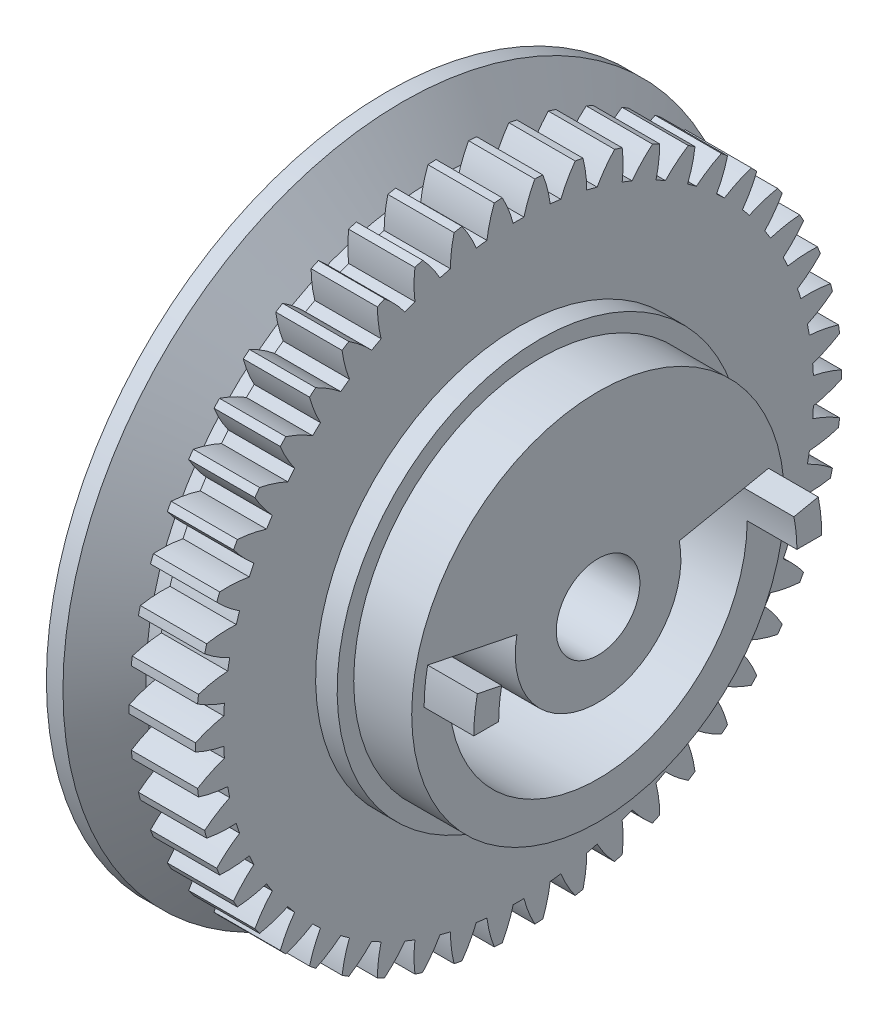
SolidWorks part; units mm, degrees
ref_plane "Plane1" through (0, 0, 0) normal (0, 0, 1) x (1, 0, 0)
ref_plane "Plane2" through (0, 0, 0) normal (0, 1, 0) x (1, 0, 0)
ref_plane "Plane3" through (0, 0, 0) normal (1, 0, 0) x (0, 0, -1)
other "Configuration Table"
sketch "HoldingSke" plane through (0, 0, 0) normal (0, 1, 0) x (1, 0, 0)
  line L0 (0, 0) -> (0.4285, -0.5107)
  line L1 (-15, 0) -> (100, 0) construction
  line L2 (0, 0) -> (-2.1039, 2.3779)
  line L3 (0, 0) -> (-11.863, 4.5341)
  line L4 (0, 0) -> (5.5511, 6.6156)
  line L5 (0, 0) -> (-46.8476, -17.4728)
  line L6 (0, 0) -> (-6.6317, -4.4744)
  line L7 (-2.1039, 2.3779) -> (8.6586, 51.2059)
  line L8 (-76.2, 54.61) -> (-74.4, 54.61)
  line L9 (-71.009, 38.7566) -> (-53.1078, 45.2721)
  line L10 (-76.2, 71.12) -> (104.1128, 71.12)
  line L11 (0, 0) -> (-8, 0)
  line L12 (-76.2, 101.6) -> (-76.147, 101.6)
  line L13 (24.9733, 27.94) -> (52.9518, 28.4284)
  line L14 (24.9733, 27.94) -> (24.9743, 27.94)
  line L15 (24.9733, 27.94) -> (100.4006, 29.5858)
  line L16 (-63.627, -1.5) -> (-12.827, -1.5)
  circle A0 centre (0, 0) radius 5
  circle A1 centre (0, 0) radius 35.624
  circle A2 centre (0, 0) radius 37.5
  circle A3 centre (0, 0) radius 5
  dimension "MHD" = 71.248
  dimension "Hub_dia" = 75
  dimension "Bore" = 10
  dimension "MBD" = 10
  dimension "Num_teeth" = 50
  dimension "Pitch" = 0.6667
  dimension "Overall_len" = 50
  dimension "Show_teeth" = 50
  dimension "Thickness" = 8
  dimension "OAL" = 50.0001
  dimension "T_dim" = 1.8
  dimension "Ap" = 20
  dimension "H" = 19.05
  dimension "Pitch_radius" = 180.3128
  dimension "Width" = 8
  dimension "Backlash" = 0.053
  dimension "Addendum_fac" = 1
  dimension "Dedendum_fac" = 1.25
  dimension "Clearance_fac" = 0.25
  dimension "Dedendum_add" = 0.001
  dimension "Module" = 1.5
sketch "BasProSke" plane through (0, 0, 0) normal (0, 1, 0) x (1, 0, 0)
  line L0 (-10, 0) -> (60, 0) construction
  line L1 (0, 0) -> (0, 39)
  line L2 (0, 0) -> (8, 0)
  line L3 (8, 0) -> (8, 39)
  line L4 (8, 39) -> (0, 39)
  dimension "Thickness" = 8
  dimension "Diameter" = 78
revolve "Base-Revolve" add sketch "BasProSke" angle 360 about L0
sketch "TooCutSke" plane through (0, 0, 0) normal (1, 0, 0) x (0, 0, -1)
  line L1 (0, 0) -> (0, 107) construction
  line L2 (0, 0) -> (-1.2706, 37.4785) construction
  line L3 (0, 0) -> (-4.7073, 74.8207) construction
  line L4 (-1.2706, 37.4785) -> (-2.3537, 37.4103) construction
  arc A0 (0.65, 35.6181) -> (-0.65, 35.6181) centre (0, 0) ccw
  arc A1 (1.9801, 38.9751) -> (-1.9801, 38.9751) centre (0, 0) ccw
  circle A2 centre (0, 0) radius 37.5 construction
  circle A3 centre (0, 0) radius 35.2385 construction
  arc A4 (-0.65, 35.6181) -> (-1.9801, 38.9751) centre (-15.1589, 31.8113) ccw
  arc A5 (1.9801, 38.9751) -> (0.65, 35.6181) centre (15.1589, 31.8113) ccw
  dimension "Root_dia" = 71.248
  dimension "Overcut_dia" = 78.0508
  dimension "Pitch_dia" = 75
  dimension "Base_dia" = 70.4769
  dimension "Flank_rad" = 15
  dimension "Half_ang" = 3.6
  dimension "Half_CT" = 1.0852
extrude "ToothCut" cut sketch "TooCutSke" along normal through all
fillet "Breaks" [suppressed] radius 0.03 tangent propagation no
fillet "RootFillets" [suppressed] radius 0.376
pattern_circular "TeethCuts" count 50 every 7.2 about axis through (-10, 0, 0) along (1, 0, 0) of "ToothCut", "RootFillets", "Breaks"
sketch "HubNeaOneSke" plane through (0, 0, 0) normal (-1, 0, 0) x (0, 0, 1)
  circle A0 centre (0, 0) radius 35.624
  dimension "Diameter" = 71.248
extrude "HubNearOne" [suppressed] add sketch "HubNeaOneSke" along normal blind 42.0001
sketch "HubNeaBotSke" plane through (0, 0, 0) normal (-1, 0, 0) x (0, 0, 1)
  circle A0 centre (0, 0) radius 35.624
  dimension "Diameter" = 71.248
extrude "HubNearBoth" [suppressed] add sketch "HubNeaBotSke" along normal blind 21
ref_plane "FarPln" through (8, 0, 0) normal (1, 0, 0) x (0, 0, -1)
sketch "HubFarSke" plane through (8, 0, 0) normal (1, 0, 0) x (0, 0, -1)
  circle A0 centre (0, 0) radius 35.624
  dimension "Diameter" = 71.248
extrude "HubFar" [suppressed] add sketch "HubFarSke" along normal blind 21
sketch "BorSke" plane through (0, 0, 0) normal (1, 0, 0) x (0, 0, -1)
  circle A0 centre (0, 0) radius 5
  dimension "Diameter" = 10
extrude "Bore" cut sketch "BorSke" along normal mid plane 100.0001
sketch "KeySke" plane through (0, 0, 0) normal (1, 0, 0) x (0, 0, -1)
  line L0 (-2, 0) -> (-2, 6.8)
  line L1 (-2, 6.8) -> (2, 6.8)
  line L2 (2, 6.8) -> (2, 0)
  line L3 (0, 0) -> (0, 34) construction
  line L4 (-2, 0) -> (2, 0)
  dimension "Offset" = 6.8
  dimension "Width" = 4
extrude "Keyway" [suppressed] cut sketch "KeySke" along normal mid plane 100.0001
pattern_circular "Keyway2" [suppressed] count 2 every 90 about axis through (-10, 0, 0) along (1, 0, 0) reverse direction yes
sketch "草图1" plane through (0, 0, 0) normal (0, 0, 1) x (1, 0, 0)
  line L0 (8, 24.5) -> (10.6, 24.5)
  line L1 (8, -5) -> (8, 5) construction
  line L2 (10.6, 24.5) -> (10.6, 22.5)
  line L3 (10.6, 22.5) -> (17.6, 22.5)
  line L4 (17.6, 22.5) -> (17.6, 5)
  line L5 (17.6, 5) -> (8, 5)
  line L6 (8, 5) -> (8, 24.5)
  line L7 (-8, 5) -> (0, 5)
  line L8 (0, 0) -> (-5.2993, 0) construction
  line L9 (0, 0.4829) -> (0, -0.4829) construction
  line L10 (0, 5) -> (0, 35)
  line L11 (0, 35) -> (-2, 35)
  line L12 (-2, 35) -> (-6, 41)
  line L13 (-6, 41) -> (-8, 41)
  line L14 (-8, 41) -> (-8, 5)
  line L15 (0, 0) -> (0, 107) construction
  dimension "D1" = 45
  dimension "D2" = 2
  dimension "D3" = 2.6
  dimension "D4" = 7
  dimension "D5" = 10
  dimension "D6" = 82
  dimension "D7" = 70
  dimension "D8" = 2
  dimension "D9" = 2
  dimension "D10" = 8
revolve "旋转1" add sketch "草图1" angle 360 about L8
ref_axis "基准轴1" through (17.6, 0, 0) along (-1, 0, 0)
sketch "草图2" plane through (-8, 0, 0) normal (-1, 0, 0) x (0, 0, 1)
  circle A0 centre (0, 0) radius 7.5
  dimension "D1" = 15
extrude "切除-拉伸1" cut sketch "草图2" against normal blind 5.5
sketch "草图10" plane through (-8, 0, 0) normal (-1, 0, 0) x (0, 0, 1)
  circle A0 centre (0, 0) radius 5.05
  point P2 (0, 0)
  point P3 (0, 0)
  dimension "D1" = 10.1
extrude "切除-拉伸5" cut sketch "草图10" against normal through all
sketch "草图3" plane through (-8, 0, 0) normal (-1, 0, 0) x (0, 0, 1)
  line L0 (0, 0) -> (0, -18.4341) construction
  arc A0 (-7.5, -6.6144) -> (7.5, -6.6144) centre (0, 0) ccw
  arc A1 (-13.5, -11.9059) -> (13.5, -11.9059) centre (0, 0) ccw
  arc A2 (-13.5, -11.9059) -> (-7.5, -6.6144) centre (-10.5, -9.2601) cw
  arc A3 (7.5, -6.6144) -> (13.5, -11.9059) centre (10.5, -9.2601) cw
  dimension "D1" = 10
  dimension "D2" = 18
  dimension "D3" = 15
extrude "切除-拉伸2" cut sketch "草图3" against normal through all
sketch "草图4" plane through (17.6, 0, 0) normal (1, 0, 0) x (0, 0, -1)
  line L0 (14, 0) -> (-14, 0) construction
  circle A0 centre (-14, 0) radius 1.1
  circle A1 centre (14, 0) radius 1.1
  point P8 (0, 0)
  dimension "D3" = 2.2
  dimension "D1" = 28
extrude "切除-拉伸3" cut sketch "草图4" against normal up to surface (25.6 mm away) up to face at (-8, -10.1301, 0)
sketch "草图5" plane through (17.6, 0, 0) normal (1, 0, 0) x (0, 0, -1)
  line L0 (-17.6363, 3.6) -> (-9.798, 2)
  line L1 (17.6363, 3.6) -> (9.798, 2)
  line L2 (-7.6844, 0) -> (0, 0) construction
  arc A1 (9.798, 2) -> (-9.798, 2) centre (0, 0) cw
  arc A3 (17.6363, 3.6) -> (-17.6363, 3.6) centre (0, 0) cw
  arc A6 (-13.5, -11.9059) -> (13.5, -11.9059) centre (0, 0) ccw construction
  arc A7 (-7.5, -6.6144) -> (7.5, -6.6144) centre (0, 0) ccw construction
  dimension "D1" = 2
extrude "切除-拉伸4" cut sketch "草图5" against normal offset from surface (13.6 mm away) 12 up to face at (-8, -1.1, -14)
sketch "草图7" plane through (17.6, 0, 0) normal (1, 0, 0) x (0, 0, -1)
  line L0 (17.6363, 3.6) -> (20.5757, 4.2)
  line L1 (18, 0) -> (21, 0)
  line L2 (-17.6363, 3.6) -> (-20.5757, 4.2)
  line L3 (-18, 0) -> (-21, 0)
  circle A0 centre (0, 0) radius 18
  circle A1 centre (0, 0) radius 21
  arc A2 (-17.6363, 3.6) -> (17.6363, 3.6) centre (0, 0) ccw construction
  arc M10 (17.6363, 3.6) -> (-17.6363, 3.6) centre (0, 0) cw
  dimension "D1" = 3
extrude "凸台-拉伸1" add sketch "草图7" along normal blind 6 contours L2 A1 L3 M10 | L1 A1 L0 M10 region at (17.6, 1.9605, -19.4067) region at (17.6, 1.9605, 19.4067)
equation "' \"Module@HoldingSke\" = 6.35"
equation "' \"Num_teeth@HoldingSke\" = 12"
equation "' \"Ap@HoldingSke\" =  20"
equation "' \"Ap@HoldingSke\" = 20"
equation "' \"Width@HoldingSke\" = 0.5 * 25.4"
equation "' \"Hub_dia@HoldingSke\"= 1 * 25.4"
equation "' \"Hub_dia@HoldingSke\" = 1 * 25.4"
equation "' \"Overall_len@HoldingSke\" = 1.0 * 25.4"
equation "' \"Bore@HoldingSke\" = 0.75 * 25.4"
equation "' \"T_dim@HoldingSke\" = 0.1 * 25.4"
equation "' \"Width@KeySke\" = 0.25 * 25.4"
equation "' \"Show_teeth@HoldingSke\" = 13"
equation "' \"Backlash@HoldingSke\" = 0.009 * 25.4"
equation "' \"Addendum_fac@HoldingSke\" = 1.0"
equation "' \"Dedendum_fac@HoldingSke\" = 1.25"
equation "' \"Dedendum_add@HoldingSke\" = 0.00005 * 25.4"
equation "' \"Clearance_fac@HoldingSke\" = 0.25"
equation "\"Pitch@HoldingSke\" = 1 / \"Module@HoldingSke\""
equation "\"Overcut_dia@TooCutSke\" = (\"Num_teeth@HoldingSke\" + 2 * \"Addendum_fac@HoldingSke\") / \"Pitch@HoldingSke\" + 0.002 * 25.4"
equation "\"Pitch_dia@TooCutSke\" = \"Num_teeth@HoldingSke\" / \"Pitch@HoldingSke\""
equation "\"Base_dia@TooCutSke\" = \"Num_teeth@HoldingSke\" / \"Pitch@HoldingSke\" * cos((\"Ap@HoldingSke\"  * 3.14159265 / 180))"
equation "\"Root_dia@TooCutSke\" = (\"Num_teeth@HoldingSke\" + 2) / \"Pitch@HoldingSke\" - 2 * (\"Addendum_fac@HoldingSke\" + \"Dedendum_fac@HoldingSke\") / \"Pitch@HoldingSke\" - \"Dedendum_add@HoldingSke\" * 2"
equation "\"Half_ang@TooCutSke\" = 180 / \"Num_teeth@HoldingSke\""
equation "\"Half_CT@TooCutSke\" = \"Num_teeth@HoldingSke\" / \"Pitch@HoldingSke\" * sin((3.14159265 / 2 / \"Num_teeth@HoldingSke\")) / 2 - 7 * \"Backlash@HoldingSke\" / 4"
equation "\"Flank_rad@TooCutSke\" = \"Num_teeth@HoldingSke\" / \"Pitch@HoldingSke\" / 5"
equation "\"Radius@RootFillets\" = \"Clearance_fac@HoldingSke\" / \"Pitch@HoldingSke\" + \"Dedendum_add@HoldingSke\""
equation "\"Break_rad@Breaks\" = 0.02 / \"Pitch@HoldingSke\""
equation "\"Thickness@HoldingSke\" = \"Width@HoldingSke\""
equation "\"OAL@HoldingSke\" = \"Thickness@HoldingSke\""
equation "\"MHD@HoldingSke\" = (\"Num_teeth@HoldingSke\" + 2) / \"Pitch@HoldingSke\" - 2 * (\"Addendum_fac@HoldingSke\" + \"Dedendum_fac@HoldingSke\")  / \"Pitch@HoldingSke\" - \"Dedendum_add@HoldingSke\" * 2"
equation "\"MBD@HoldingSke\" = (\"Num_teeth@HoldingSke\" + 2) / \"Pitch@HoldingSke\" - 2 * (\"Addendum_fac@HoldingSke\" + \"Dedendum_fac@HoldingSke\")  / \"Pitch@HoldingSke\" - \"Dedendum_add@HoldingSke\" * 2 - 0.002 * 25.4"
equation "\"MHD@HoldingSke\" = ((sgn( \"MHD@HoldingSke\" - \"Hub_dia@HoldingSke\" )-1)*( \"MHD@HoldingSke\" - \"Hub_dia@HoldingSke\" ))/-2+ \"Hub_dia@HoldingSke\""
equation "\"MBD@HoldingSke\" = ((sgn( \"MBD@HoldingSke\" - \"Bore@HoldingSke\" )-1)*( \"MBD@HoldingSke\" - \"Bore@HoldingSke\" ))/-2+ \"Bore@HoldingSke\""
equation "\"OAL@HoldingSke\" = ((sgn( \"OAL@HoldingSke\" - \"Overall_len@HoldingSke\" )+1)*( \"OAL@HoldingSke\" - \"Overall_len@HoldingSke\" ))/2 + \"Overall_len@HoldingSke\" + 0.000002 * 25.4"
equation "\"Num_teeth@TeethCuts\" = int( \"Show_teeth@HoldingSke\" ) + 1"
equation "\"Num_teeth@TeethCuts\" = ((sgn( \"Num_teeth@TeethCuts\" - \"Num_teeth@HoldingSke\" )-1)*( \"Num_teeth@TeethCuts\" - \"Num_teeth@HoldingSke\" ))/-2+ \"Num_teeth@HoldingSke\""
equation "\"Num_teeth@TeethCuts\" = ((sgn( \"Num_teeth@TeethCuts\" - 2.0)+1)*( \"Num_teeth@TeethCuts\" - 2.0))/2 +2.0"
equation "\"Angle@TeethCuts\" = 360.0 / \"Num_teeth@HoldingSke\""
equation "\"Diameter@BasProSke\" = (\"Num_teeth@HoldingSke\" + 2 * \"Addendum_fac@HoldingSke\") / \"Pitch@HoldingSke\""
equation "\"Thickness@BasProSke\"  = \"Thickness@HoldingSke\""
equation "' \"Fillet_rad@BasProSke\" =  \"Thickness@HoldingSke\" * 0.05"
equation "' \"Fillet_rad@BasProSke\" = \"Thickness@HoldingSke\" * 0.05"
equation "\"MHD@HoldingSke\" = ((sgn( \"MHD@HoldingSke\" - \"Root_dia@TooCutSke\" )-1)*( \"MHD@HoldingSke\" - \"Root_dia@TooCutSke\" ))/-2+ \"Root_dia@TooCutSke\""
equation "\"Diameter@HubNeaOneSke\" = \"MHD@HoldingSke\""
equation "\"Length@HubNearOne\" = \"OAL@HoldingSke\" - \"Thickness@BasProSke\""
equation "\"Diameter@HubNeaBotSke\" = \"MHD@HoldingSke\""
equation "\"Length@HubNearBoth\" = ( \"OAL@HoldingSke\" - \"Thickness@BasProSke\" ) / 2.0"
equation "\"Thickness@FarPln\" = \"Thickness@BasProSke\""
equation "\"Diameter@HubFarSke\" = \"MHD@HoldingSke\""
equation "\"Length@HubFar\" = ( \"OAL@HoldingSke\" - \"Thickness@BasProSke\" ) / 2.0"
equation "\"Diameter@BorSke\" = \"MBD@HoldingSke\""
equation "\"D1@Bore\" = \"OAL@HoldingSke\" * 2.0"
equation "\"D1@Keyway\" = \"OAL@HoldingSke\" * 2.0"
equation "\"Offset@KeySke\" = \"T_dim@HoldingSke\" + \"MBD@HoldingSke\" / 2.0"
